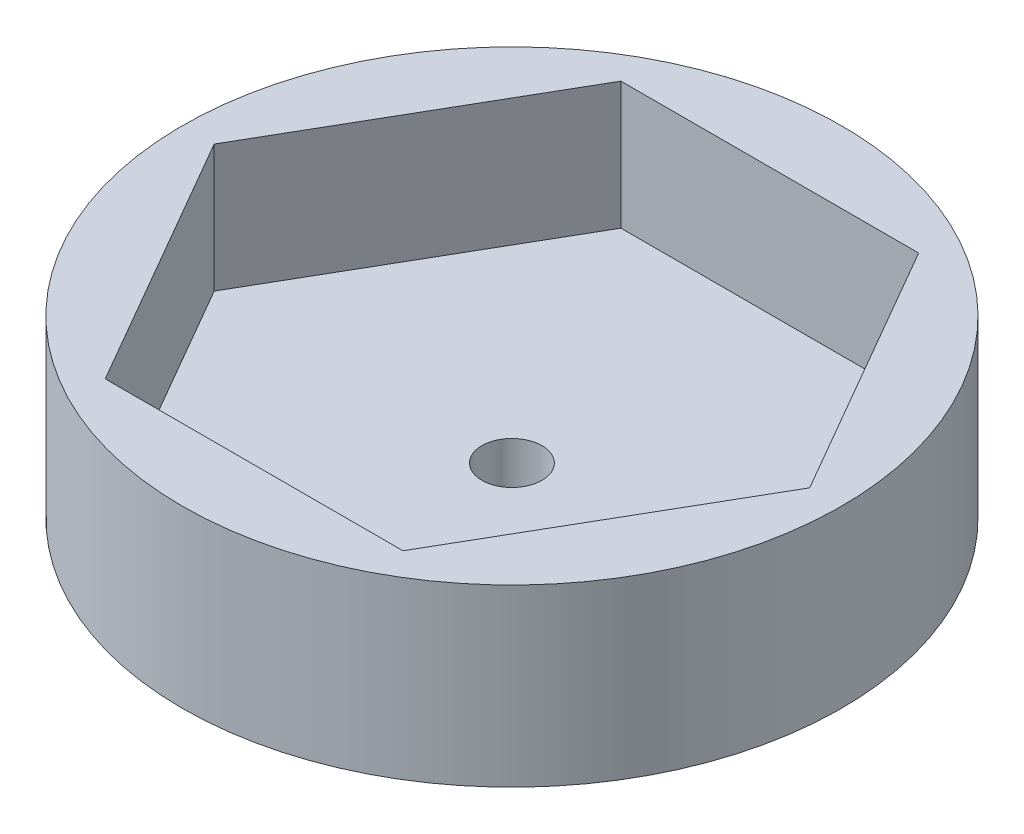
SolidWorks part; units mm, degrees
material "ABS"
ref_plane "Front Plane" through (0, 0, 0) normal (0, 0, 1) x (1, 0, 0)
ref_plane "Top Plane" through (0, 0, 0) normal (0, 1, 0) x (1, 0, 0)
ref_plane "Right Plane" through (0, 0, 0) normal (1, 0, 0) x (0, 0, -1)
sketch "Sketch1" plane through (0, 0, 0) normal (0, 1, 0) x (1, 0, 0)
  circle A0 centre (0, 0) radius 93.5205
  circle A1 centre (0, 0) radius 9.4375
  dimension "D1" = 18.875
  dimension "D2" = 187.041
extrude "Boss-Extrude1" add sketch "Sketch1" along normal blind 15
sketch "Sketch2" plane through (0, 15, 0) normal (0, 1, 0) x (1, 0, 0)
  circle A1 centre (0, 0) radius 93.5205 construction
  circle A2 centre (0, 0) radius 93.5205
  circle A4 centre (0, 0) radius 103.5205
  dimension "D1" = 10
extrude "Boss-Extrude2" add sketch "Sketch2" along normal blind 40 and the other way up to surface (15 mm away) other way up to face at (0, 0, 93.5205)
sketch "Sketch3" plane through (0, 15, 0) normal (0, 1, 0) x (1, 0, 0)
  line L1 (93.5205, 0) -> (46.7603, 80.9911)
  line L2 (46.7603, 80.9911) -> (-46.7602, 80.9911)
  line L3 (-46.7602, 80.9911) -> (-93.5205, 0)
  line L4 (-93.5205, 0) -> (-46.7603, -80.9911)
  line L5 (-46.7603, -80.9911) -> (46.7602, -80.9911)
  line L6 (46.7602, -80.9911) -> (93.5205, 0)
  circle A0 centre (0, 0) radius 93.5205 construction
  circle A1 centre (0, 0) radius 93.5205 construction
  circle M7 centre (0, 0) radius 93.5205
extrude "Boss-Extrude3" add sketch "Sketch3" along normal up to surface (40 mm away) contours L4 M7 | L3 M7 | L2 M7 | L1 M7 | L6 M7 | L5 M7 region at (74.5066, 15, 43.0164) region at (74.5066, 15, -43.0164) region at (0, 15, -86.0328) region at (0, 15, 86.0328) region at (-74.5066, 15, -43.0164) region at (-74.5066, 15, 43.0164) up to face at (0, 55, 103.5205)
equation "\"Rope\"= 5in / 8"
equation "\"D1@Sketch1\"=\"Rope\"+1in\\8"
